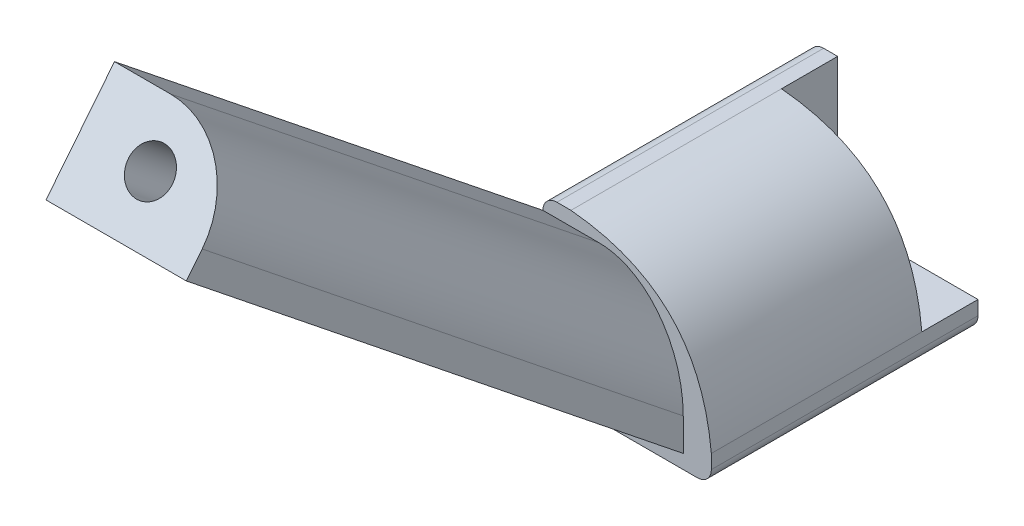
SolidWorks part; units mm, degrees
ref_plane "Front Plane" through (0, 0, 0) normal (0, 0, 1) x (1, 0, 0)
ref_plane "Top Plane" through (0, 0, 0) normal (0, 1, 0) x (1, 0, 0)
ref_plane "Right Plane" through (0, 0, 0) normal (1, 0, 0) x (0, 0, -1)
sketch "Sketch1" plane through (0, 0, 0) normal (0, 0, 1) x (1, 0, 0)
  line L0 (0, 0) -> (12.7, 0)
  line L1 (0, 0) -> (0, 12.7)
  circle A0 centre (5.08, 5.08) radius 3.1115
  spline S0 degree 2 poles (0, 12.7) (11.6203, 11.6203) (12.7, 0) knots 0 0 0 1 1 1
  dimension "D5" = 6.223
  dimension "D1" = 12.7
  dimension "D2" = 12.7
  dimension "D3" = 5.08
  dimension "D4" = 5.08
extrude "Boss-Extrude1" add sketch "Sketch1" along normal blind 3.81
sketch "Sketch2" plane through (0, 0, 0) normal (0, 0, -1) x (-1, 0, 0)
  line L0 (0, 12.7) -> (1.27, 12.7)
  line L1 (2.54, 11.43) -> (2.54, -1.27)
  line L2 (0, 12.7) -> (0, 0) construction
  line L3 (-12.7, 0) -> (-12.7, -1.27)
  line L4 (-11.43, -2.54) -> (1.27, -2.54)
  line L5 (0, 12.7) -> (0, 0)
  line L6 (0, 0) -> (-12.7, 0)
  arc A0 (1.27, 12.7) -> (2.54, 11.43) centre (1.27, 11.43) cw
  arc A1 (-12.7, -1.27) -> (-11.43, -2.54) centre (-11.43, -1.27) ccw
  arc A2 (1.27, -2.54) -> (2.54, -1.27) centre (1.27, -1.27) ccw
  point P14 (-12.7, -2.54)
  dimension "D3" = 1.27
  dimension "D1" = 2.54
  dimension "D2" = 2.54
extrude "Boss-Extrude2" add sketch "Sketch2" along normal blind 5.08 and the other way blind 3.81 contours L1 A2 L4 A1 L3 L6 L5 L0 A0
sketch "Sketch3" plane through (0, 0, 3.81) normal (0, 0, 1) x (1, 0, 0)
  line L0 (-2.54, 11.43) -> (-2.54, -1.27)
  line L1 (-1.27, -2.54) -> (11.43, -2.54)
  line L2 (12.7, -1.27) -> (12.7, 0)
  line L3 (-1.27, 12.7) -> (0, 12.7)
  arc A0 (11.43, -2.54) -> (12.7, -1.27) centre (11.43, -1.27) ccw
  arc A1 (-2.54, 11.43) -> (-1.27, 12.7) centre (-1.27, 11.43) cw
  circle A2 centre (5.08, 5.08) radius 1.2
  arc A3 (-2.54, -1.27) -> (-1.27, -2.54) centre (-1.27, -1.27) ccw
  spline S0 degree 2 poles (0, 12.7) (11.6203, 11.6203) (12.7, 0) knots 0 0 0 1 1 1
  dimension "D1" = 1.27
  dimension "D2" = 2.4
  dimension "D3" = 1.27
extrude "Boss-Extrude3" add sketch "Sketch3" along normal blind 2.54
sketch "Sketch4" plane through (0, 0, 6.35) normal (0, 0, 1) x (1, 0, 0)
  line L0 (-2.54, 11.43) -> (-2.54, -1.27)
  line L1 (-1.27, -2.54) -> (11.43, -2.54)
  line L2 (12.7, -1.27) -> (12.7, 0)
  line L3 (-1.27, 12.7) -> (0, 12.7)
  arc A0 (11.43, -2.54) -> (12.7, -1.27) centre (11.43, -1.27) ccw
  arc A1 (-2.54, 11.43) -> (-1.27, 12.7) centre (-1.27, 11.43) cw
  circle A2 centre (5.08, 5.08) radius 3.175
  arc A3 (-2.54, -1.27) -> (-1.27, -2.54) centre (-1.27, -1.27) ccw
  spline S0 degree 2 poles (0, 12.7) (11.6203, 11.6203) (12.7, 0) knots 0 0 0 1 1 1
  dimension "D1" = 1.27
  dimension "D2" = 6.35
  dimension "D3" = 1.27
extrude "Boss-Extrude4" add sketch "Sketch4" along normal blind 12.7
sketch "Sketch8" plane through (-2.54, 0, 0) normal (-1, 0, 0) x (0, 0, 1)
  line L3 (19.05, 11.43) -> (19.05, -1.27)
  line L5 (19.05, 11.43) -> (57.8146, 42.4641)
  line L6 (19.05, 11.43) -> (-5.08, 11.43) construction
  line L7 (19.05, -1.27) -> (64.0107, 34.7245)
  line L8 (19.05, -1.27) -> (-5.08, -1.27) construction
  line L9 (64.0107, 34.7245) -> (57.8146, 42.4641)
  point P10 (48.028, 34.6292)
  point P11 (48.886, 35.316)
  dimension "D1" = 141.32
  dimension "D2" = 141.32
  dimension "D3" = 57.594
extrude "Boss-Extrude5" add sketch "Sketch8" against normal blind 12.7
sketch "Sketch7" plane through (0, 0, 19.05) normal (0, 0, 1) x (1, 0, 0)
  circle A0 centre (5.08, 5.08) radius 3.1115
extrude "Cut-Extrude1" cut sketch "Sketch7" along normal through all
sketch "Sketch9" plane through (0, 44.7926, 55.9504) normal (0, 0.625, 0.7806) x (1, 0, 0)
  circle A0 centre (3.81, -7.94) radius 2
  dimension "D1" = 4
extrude "Cut-Extrude2" cut sketch "Sketch9" against normal blind 7
fillet "Fillet1" radius 7.62 1 edges at (10.16, 26.947, 38.4323)
